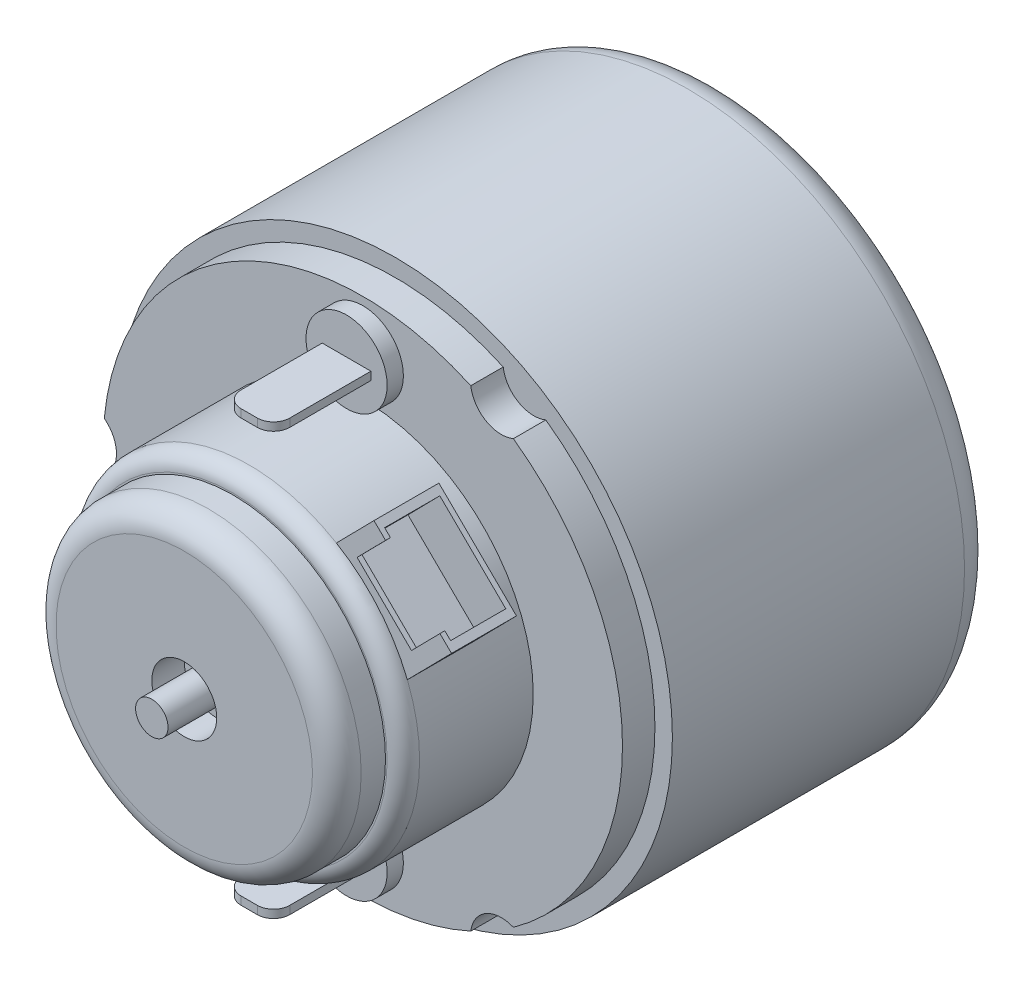
SolidWorks part; units mm, degrees
note: '?' marks a value the reader was unsure of.
ref_plane "Plano frontal" through (0, 0, 0) normal (0, 0, 1) x (1, 0, 0)
ref_plane "Plano superior" through (0, 0, 0) normal (0, 1, 0) x (1, 0, 0)
ref_plane "Plano direito" through (0, 0, 0) normal (1, 0, 0) x (0, 0, -1)
sketch "Esboço1" plane through (0, 0, 0) normal (0, 0, 1) x (1, 0, 0)
  circle A0 centre (0, 0) radius 17.075
  dimension "D1" = 34.15
extrude "Ressalto-extrusão1" add sketch "Esboço1" along normal blind 20
sketch "Esboço4" plane through (0, 0, 0) normal (0, 0, -1) x (-1, 0, 0)
  line L0 (0, 0) -> (-11.2583, -6.5) construction
  line L1 (0, 0) -> (0, 13) construction
  line L2 (0, 0) -> (11.2583, -6.5) construction
  circle A0 centre (0, 0) radius 3.5
  circle A1 centre (0, 13) radius 1.25
  circle A2 centre (11.2583, -6.5) radius 1.25
  circle A3 centre (-11.2583, -6.5) radius 1.25
  dimension "D1" = 7
  dimension "D2" = 2.5
  dimension "D3" = 2.5
  dimension "D4" = 2.5
  dimension "D5" = 13
  dimension "D6" = 120
  dimension "D7" = 13
  dimension "D8" = 120
  dimension "D9" = 13
extrude "Ressalto-extrusão4" add sketch "Esboço4" along normal blind 1.5 contours A0
sketch "Esboço14" plane through (0, 0, -1.5) normal (0, 0, -1) x (-1, 0, 0)
  circle A0 centre (0, 0) radius 1
  dimension "D1" = 2
extrude "Ressalto-extrusão7" add sketch "Esboço14" along normal blind 3.5
hole_wizard "Furo roscado de M2.5x0.451" positions "Esboço16" profile "Esboço15" tap size "M2.5x0.45" standard "Métrico Ansi"
sketch "Esboço16" plane through (0, 0, 0) normal (0, 0, -1) x (-1, 0, 0)
  line L0 (0, 13) -> (0, 0) construction
  line L1 (0, 0) -> (11.2583, -6.5) construction
  line L3 (0, 0) -> (-11.2583, -6.5) construction
  line L4 (0, 0) -> (11.2583, 6.5) construction
  line L6 (0, 0) -> (0, -13) construction
  line L8 (0, 0) -> (-11.2583, 6.5) construction
  point P0 (11.2583, -6.5)
  point P1 (0, 13)
  point P3 (-11.2583, -6.5)
  point P31 (11.2583, 6.5)
  point P33 (0, -13)
  point P35 (-11.2583, 6.5)
  dimension "D1" = 13
  dimension "D2" = 13
  dimension "D3" = 13
  dimension "D4" = 120
  dimension "D5" = 120
  dimension "D6" = 13
  dimension "D7" = 13
  dimension "D8" = 13
  dimension "D9" = 120
  dimension "D10" = 120
  dimension "D11" = 60
sketch "Esboço15" plane through (-11.2583, -6.5, 0) normal (1, 0, 0) x (0, 1, 0)
  line L0 (0, 0) -> (0, 4.1159)
  line L1 (0, 4.1159) -> (1.025, 3.5)
  line L2 (1.025, 3.5) -> (1.025, 0)
  line L5 (1.025, 0) -> (0, 0)
  line L10 (0, 4.1159) -> (-1.025, 3.5) construction
  line L11 (0, -6.35) -> (0, 107.95) construction
  dimension "Tap Drill Dia." = 2.05
  dimension "Tap Drill Depth" = 3.5
  dimension "Drill Angle" = 118
ref_axis "Eixo1" through (0, 0, -9.675) along (0, 0, 1)?
fillet "Filete1" radius 2 1 edges at (17.075, 0, 0)
sketch "Esboço17" plane through (0, 0, 20) normal (0, 0, 1) x (1, 0, 0)
  line L0 (0, 0) -> (8.5375, 14.7874) construction
  line L1 (0, 0) -> (-17.075, 0) construction
  line L2 (0, 0) -> (8.5375, -14.7874) construction
  arc A0 (9.2759, -13.0368) -> (9.2759, 13.0368) centre (0, 0) ccw
  circle A1 centre (0, 0) radius 17.075
  arc A2 (6.8417, -15.6444) -> (10.1275, -13.7473) centre (0, 0) ccw
  arc A3 (-16.9693, -1.8971) -> (-16.9693, 1.8971) centre (-17.075, 0) ccw
  arc A4 (10.1275, -13.7473) -> (6.8417, -15.6444) centre (8.5375, -14.7874) ccw
  arc A5 (6.8417, 15.6444) -> (10.1275, 13.7473) centre (8.5375, 14.7874) ccw
  arc A6 (10.1275, 13.7473) -> (6.8417, 15.6444) centre (0, 0) ccw
  arc A7 (6.6522, 14.5516) -> (6.6522, -14.5516) centre (0, 0) ccw
  arc A8 (-16.9693, 1.8971) -> (-16.9693, -1.8971) centre (0, 0) ccw
  dimension "D4" = 3.8
  dimension "D5" = 3.8
  dimension "D6" = 3.8
  dimension "D7" = 32
  dimension "D2" = 120
  dimension "D3" = 120
  dimension "D1" = 0
extrude "Ressalto-extrusão9" add sketch "Esboço17" along normal blind 2 contours A5 A2 A3 A4
sketch "Esboço18" plane through (0, 0, 22) normal (0, 0, 1) x (1, 0, 0)
  circle A0 centre (0, 0) radius 10.5
  dimension "D1" = 21
extrude "Ressalto-extrusão10" add sketch "Esboço18" along normal blind 8
fillet "Filete2" radius 1 1 edges at (10.5, 0, 30)
sketch "Esboço19" plane through (0, 0, 30) normal (0, 0, 1) x (1, 0, 0)
  circle A0 centre (0, 0) radius 9.4
  dimension "D1" = 18.8
extrude "Ressalto-extrusão11" add sketch "Esboço19" along normal blind 3
fillet "Filete3" radius 1.5 1 edges at (9.4, 0, 33)
sketch "Esboço20" plane through (0, 0, 33) normal (0, 0, 1) x (1, 0, 0)
  circle A0 centre (0, 0) radius 2
  dimension "D1" = 4
extrude "Corte-extrusão1" cut sketch "Esboço20" against normal blind 2
sketch "Esboço21" plane through (0, 0, 31) normal (0, 0, 1) x (1, 0, 0)
  circle A0 centre (0, 0) radius 1
  dimension "D1" = 2
extrude "Ressalto-extrusão13" add sketch "Esboço21" along normal blind 4
sketch "Esboço22" plane through (0, 0, 22) normal (0, 0, 1) x (1, 0, 0)
  line L0 (0, -13) -> (0, 0) construction
  line L1 (0, 0) -> (0, 13) construction
  circle A0 centre (0, 13) radius 2.5
  circle A1 centre (0, -13) radius 2.5
  dimension "D3" = 5
  dimension "D4" = 5
  dimension "D1" = 13
  dimension "D2" = 13
extrude "Ressalto-extrusão15" add sketch "Esboço22" along normal blind 1 separate body
sketch "Esboço23" plane through (0, 0, 23) normal (0, 0, 1) x (1, 0, 0)
  line L1 (1.5, -12.75) -> (-1.5, -12.75)
  line L2 (1.5, -12.75) -> (1.5, -13.25)
  line L3 (1.5, -13.25) -> (-1.5, -13.25)
  line L4 (-1.5, -12.75) -> (-1.5, -13.25)
  line L5 (1.5, -12.75) -> (-1.5, -13.25) construction
  line L6 (1.5, -13.25) -> (-1.5, -12.75) construction
  line L7 (1.5, 13.25) -> (-1.5, 13.25)
  line L8 (1.5, 13.25) -> (1.5, 12.75)
  line L9 (1.5, 12.75) -> (-1.5, 12.75)
  line L10 (-1.5, 13.25) -> (-1.5, 12.75)
  line L11 (1.5, 13.25) -> (-1.5, 12.75) construction
  line L12 (1.5, 12.75) -> (-1.5, 13.25) construction
  point P0 (0, -13)
  point P6 (0, 13)
  dimension "D1" = 3
  dimension "D2" = 3
  dimension "D3" = 0.5
  dimension "D4" = 0.5
extrude "Ressalto-extrusão16" add sketch "Esboço23" along normal blind 6
fillet "Filete4" radius 1 2 edges at (1.5, -13, 29) (-1.5, -13, 29)
fillet "Filete5" radius 1 2 edges at (1.5, 13, 29) (-1.5, 13, 29)
ref_plane "Plano1" through (7.3613, 7.4874, 0) normal (0.7011, 0.7131, 0) x (-0.7131, 0.7011, 0)
sketch "Esboço24" plane through (7.3613, 7.4874, 0) normal (0.7011, 0.7131, 0) x (-0.7131, 0.7011, 0)
  line L0 (10.5, 22) -> (-10.5, 22) construction
  line L1 (2.491, 29) -> (-4.209, 29)
  line L2 (2.491, 29) -> (2.491, 25)
  line L3 (2.491, 25) -> (-4.209, 25)
  line L4 (-4.209, 29) -> (-4.209, 25)
  line L5 (2.491, 29) -> (-4.209, 25) construction
  line L6 (2.491, 25) -> (-4.209, 29) construction
  line L7 (8.2196, 28) -> (8.2196, 23) construction
  point P0 (-0.859, 27)
  dimension "D1" = 6.7
  dimension "D2" = 4
  dimension "D3" = 5
  dimension "D4" = 5.7287
extrude "Ressalto-extrusão17" add sketch "Esboço24" along normal blind 3 and the other way up to next
sketch "Esboço25" plane through (9.4645, 9.6267, 0) normal (0.7011, 0.7131, 0) x (0.7131, -0.7011, 0)
  line L5 (3.709, -28.5) -> (-1.991, -28.5)
  line L6 (3.709, -28.5) -> (3.709, -28.7)
  line L7 (3.709, -28.7) -> (-1.991, -28.7)
  line L8 (3.709, -28.5) -> (3.709, -25.5)
  line L9 (3.709, -25.5) -> (-1.991, -25.5)
  line L10 (-1.991, -25.5) -> (-1.991, -28.5)
  line L11 (-1.991, -28.5) -> (3.709, -28.5)
  line L12 (3.709, -28.5) -> (3.709, -25.5)
  line L13 (3.709, -25.5) -> (-1.991, -25.5)
  line L14 (-1.991, -25.5) -> (-1.991, -28.5)
  line L15 (-1.991, -28.5) -> (3.709, -28.5)
  line L16 (-1.991, -28.5) -> (-1.991, -28.7)
  line L17 (-1.991, -25.5) -> (3.709, -25.5)
  line L18 (-1.991, -25.5) -> (-1.991, -25.3)
  line L19 (-1.991, -25.3) -> (3.709, -25.3)
  line L20 (3.709, -25.5) -> (3.709, -25.3)
  dimension "D2" = 0.2
  dimension "D3" = 0.2
  dimension "D1" = 0.5
extrude "Corte-extrusão2" cut sketch "Esboço25" against normal blind 2.8 contours L13 L14 L5 L12 | L5 L16 L7 L6 | L13 L20 L19 L18
sketch "Esboço26" plane through (9.4645, 9.6267, 0) normal (0.7011, 0.7131, 0) x (0.7131, -0.7011, 0)
  line L0 (-2.491, -29) -> (4.209, -29) construction
  line L1 (-1.491, -29) -> (3.209, -29)
  line L2 (-1.491, -29) -> (-1.491, -28.7)
  line L3 (-1.491, -28.7) -> (3.209, -28.7)
  line L4 (3.209, -29) -> (3.209, -28.7)
  line L5 (3.709, -28.7) -> (-1.991, -28.7) construction
  line L6 (-2.491, -25) -> (-2.491, -29) construction
  line L7 (4.209, -29) -> (4.209, -25) construction
  dimension "D1" = 1
  dimension "D2" = 1
extrude "Corte-extrusão3" cut sketch "Esboço26" against normal blind 2.5
ref_plane "Plano2" through (0, 0, 11) normal (0, 0, -1) x (-1, 0, 0)
